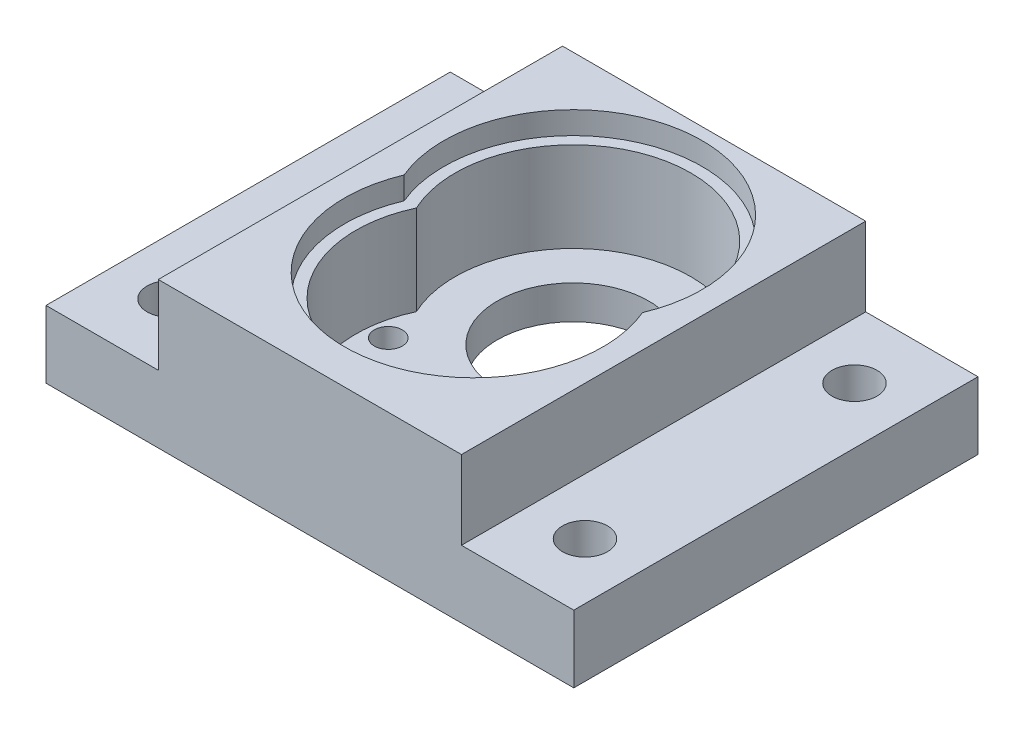
SolidWorks part; units mm, degrees
ref_plane "前视基准面" through (0, 0, 0) normal (0, 0, 1) x (1, 0, 0)
ref_plane "上视基准面" through (0, 0, 0) normal (0, 1, 0) x (1, 0, 0)
ref_plane "右视基准面" through (0, 0, 0) normal (1, 0, 0) x (0, 0, -1)
sketch "草图1" plane through (0, 0, 0) normal (0, 1, 0) x (1, 0, 0)
  line L0 (0, 0) -> (0, 23.6508) construction
  line L1 (-2.7, -10.7323) -> (2.7, -10.7323) construction
  line L2 (-8.75, 0) -> (8.75, 0) construction
  line L3 (0, 7.7) -> (0, -10.7323) construction
  line L4 (0, 0) -> (10.4267, 0) construction
  line L5 (-13.5, 20.2677) -> (-13.5, -15.7323)
  line L6 (-13.5, 20.2677) -> (13.5, 20.2677)
  line L8 (-13.5, -15.7323) -> (13.5, -15.7323)
  line L10 (13.5, 20.2677) -> (13.5, -15.7323)
  circle A0 centre (0, 7.7) radius 6.75
  circle A1 centre (0, -4.3) radius 1.5
  circle A3 centre (-8.75, 0) radius 1.25
  circle A6 centre (-2.7, -10.7323) radius 1.5
  circle A8 centre (8.75, 0) radius 1.25
  circle A9 centre (2.7, -10.7323) radius 1.5
  dimension "D3" = 13.5
  dimension "D4" = 2.5
  dimension "D7" = 3
  dimension "D12" = 3
  dimension "D1" = 7.7
  dimension "D2" = 18.4323
  dimension "D5" = 17.5
  dimension "D6" = 2.7
  dimension "D8" = 27
  dimension "D9" = 36
  dimension "D10" = 5
  dimension "D13" = 12
extrude "凸台-拉伸1" add sketch "草图1" along normal blind 3
sketch "草图4" plane through (0, 0, -20.2677) normal (0, 0, -1) x (-1, 0, 0)
  line L0 (0, 0) -> (0, 15.4348) construction
  line L1 (-13.5, 0) -> (-23.5, 0)
  line L2 (-13.5, 0) -> (-13.5, 6)
  line L3 (-13.5, 6) -> (-23.5, 6)
  line L4 (-23.5, 0) -> (-23.5, 6)
  line L5 (13.5, 0) -> (23.5, 0)
  line L6 (13.5, 0) -> (13.5, 6)
  line L7 (23.5, 0) -> (23.5, 6)
  line L8 (13.5, 6) -> (23.5, 6)
  dimension "D1" = 10
  dimension "D2" = 6
extrude "凸台-拉伸3" add sketch "草图4" against normal up to surface (36 mm away) up to face at (0, 1.5, 15.7323)
sketch "草图6" plane through (0, 0, 0) normal (0, -1, 0) x (1, 0, 0)
  circle A0 centre (-8.75, 0) radius 3
  circle A1 centre (8.75, 0) radius 3
  dimension "D1" = 6
  dimension "D2" = 6
extrude "切除-拉伸3" cut sketch "草图6" against normal blind 1
sketch "草图7" plane through (0, 3, 0) normal (0, 1, 0) x (1, 0, 0)
  line L0 (0, 20.2677) -> (0, -15.7323) construction
  line L1 (0, 0) -> (0, 24.4956) construction
  line L3 (-9.5247, 3.2807) -> (9.5247, 3.2807) construction
  line L5 (-13.5, 20.2677) -> (13.5, 20.2677)
  line L6 (-13.5, 20.2677) -> (-13.5, -15.7323)
  line L7 (-13.5, -15.7323) -> (13.5, -15.7323)
  line L8 (13.5, 20.2677) -> (13.5, -15.7323)
  line L9 (-13.5, -15.7323) -> (13.5, -15.7323) construction
  arc A1 (9.5247, 3.2807) -> (-9.5247, 3.2807) centre (0, 7.7) ccw
  arc A3 (-9.5247, 3.2807) -> (9.5247, 3.2807) centre (0, -1.1386) ccw
  circle M1 centre (2.7, -10.7323) radius 1.5
  circle M8 centre (-2.7, -10.7323) radius 1.5
  dimension "D1" = 10.5
  dimension "D2" = 10.5
  dimension "D3" = 4.4193
  dimension "D5" = 27
  dimension "D4" = 36
extrude "凸台-拉伸4" add sketch "草图7" along normal blind 10 contours A3 A1 M1 M8 region at (0, 3, -19.8177)
sketch "草图9" plane through (0, 3, 0) normal (0, 1, 0) x (1, 0, 0)
  arc A0 (9.5247, 3.2807) -> (-9.5247, 3.2807) centre (0, 7.7) ccw construction
  arc A1 (9.5247, 3.2807) -> (-9.5247, 3.2807) centre (0, 7.7) ccw
  arc A3 (10.617, 3.2807) -> (-10.617, 3.2807) centre (0, 7.7) ccw
  arc A4 (-9.5247, 3.2807) -> (9.5247, 3.2807) centre (0, -1.1386) ccw
  arc A5 (-10.617, 3.2807) -> (10.617, 3.2807) centre (0, -1.1386) ccw
  dimension "D1" = 10.5
  dimension "D2" = 1
extrude "切除-拉伸5" cut sketch "草图9" against normal blind 2 from surface contours A5 A3 starting at face at (0, 13, 4.5856)
sketch "草图11" plane through (0, 13, 0) normal (0, 1, 0) x (1, 0, 0)
  arc A0 (10.617, 3.2807) -> (-10.617, 3.2807) centre (0, 7.7) ccw construction
  arc A1 (-10.617, 3.2807) -> (10.617, 3.2807) centre (0, -1.1386) ccw construction
  circle A2 centre (-8.75, 0) radius 1.25 construction
  circle A3 centre (8.75, 0) radius 1.25 construction
  arc A4 (10.617, 3.2807) -> (-10.617, 3.2807) centre (0, 7.7) ccw
  arc A5 (-10.617, 3.2807) -> (10.617, 3.2807) centre (0, -1.1386) ccw
  circle A6 centre (-8.75, 0) radius 1.25
  circle A7 centre (8.75, 0) radius 1.25
sketch "草图13" plane through (0, 6, 0) normal (0, 1, 0) x (1, 0, 0)
  line L0 (-18.5, 20.2677) -> (-18.5, -15.7323) construction
  line L1 (-23.5, 20.2677) -> (-13.5, 20.2677) construction
  line L2 (-13.5, -15.7323) -> (-23.5, -15.7323) construction
  line L3 (0, 20.2677) -> (0, -15.7323) construction
  line L5 (13.5, 20.2677) -> (-13.5, 20.2677) construction
  line L6 (-13.5, -15.7323) -> (13.5, -15.7323) construction
  circle A0 centre (-18.5, 14.2677) radius 2
  circle A1 centre (-18.5, -9.7323) radius 2
  circle A2 centre (18.5, -9.7323) radius 2
  circle A3 centre (18.5, 14.2677) radius 2
  dimension "D3" = 4
  dimension "D4" = 4
  dimension "D1" = 6
  dimension "D2" = 6
extrude "切除-拉伸6" cut sketch "草图13" against normal blind 10
